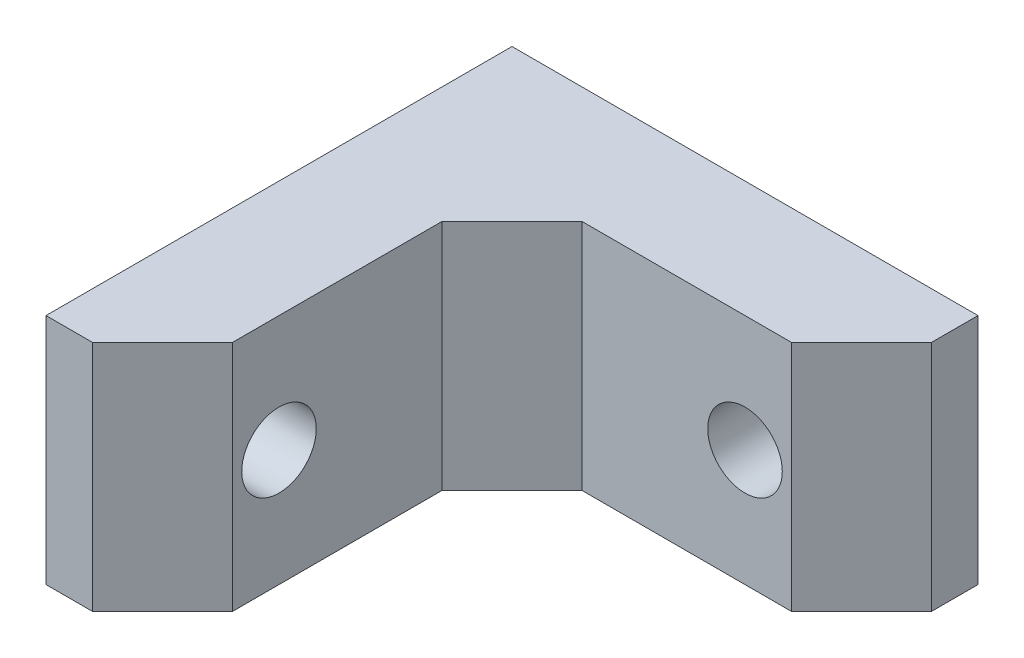
SolidWorks part; units mm, degrees
ref_plane "Ebene vorne" through (0, 0, 0) normal (0, 0, 1) x (1, 0, 0)
ref_plane "Ebene oben" through (0, 0, 0) normal (0, 1, 0) x (1, 0, 0)
ref_plane "Ebene rechts" through (0, 0, 0) normal (1, 0, 0) x (0, 0, -1)
sketch "Skizze1" plane through (0, 0, 0) normal (0, 0, 1) x (1, 0, 0)
  line L0 (5, 10) -> (5, 0)
  line L1 (0, 0) -> (20, 0)
  line L2 (0, 0) -> (0, 10)
  line L3 (0, 10) -> (20, 10)
  line L4 (20, 0) -> (20, 10)
  circle A0 centre (15, 5) radius 1.6
extrude "Aufsatz-Linear austragen1" add sketch "Skizze1" along normal blind 5 contours L1 L4 L3 L0 A0 region at (12.3584, 5, 0)
extrude "Aufsatz-Linear austragen2" add sketch "Skizze1<9>" along normal blind 20 contours L3 L2 L1 L0 region at (2.5, 5, 0)
sketch "Skizze1<9>" plane through (0, 0, 0) normal (0, 0, 1) x (1, 0, 0) same geometry as "Skizze1"
sketch "Skizze3" plane through (5, 0, 0) normal (1, 0, 0) x (0, 0, -1)
  circle A0 centre (-15, 5) radius 1.6
extrude "Schnitt-Linear austragen2" cut sketch "Skizze3" against normal blind 20
chamfer "Fase2" distance 3 angle 45 3 edges at (5, 5, 20) (20, 5, 5)
